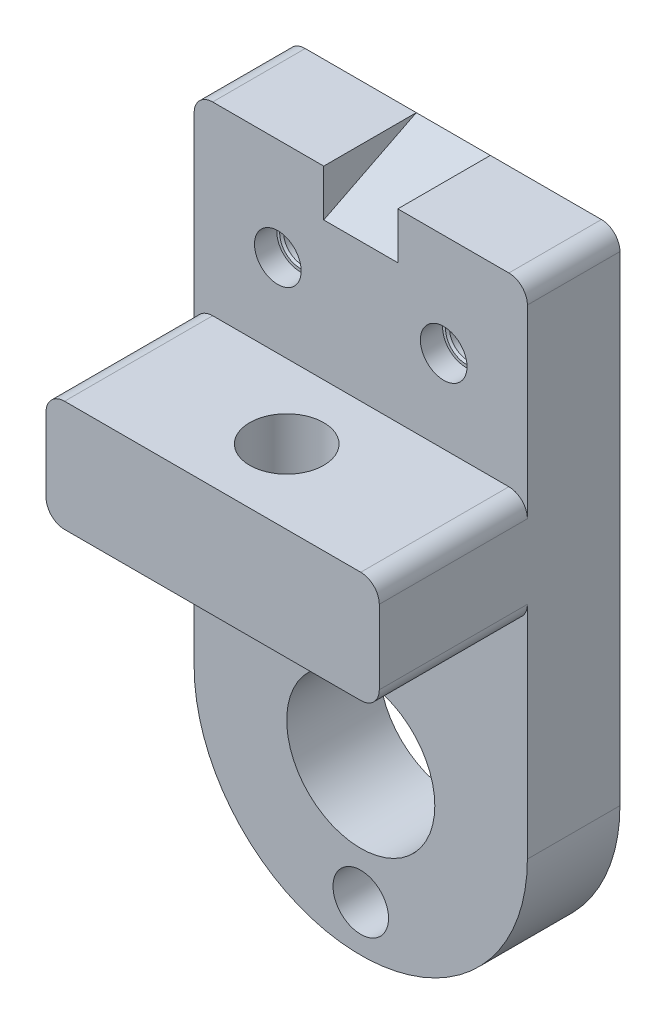
SolidWorks part; units mm, degrees
ref_plane "Alzado" through (0, 0, 0) normal (0, 0, 1) x (1, 0, 0)
ref_plane "Planta" through (0, 0, 0) normal (0, 1, 0) x (1, 0, 0)
ref_plane "Vista lateral" through (0, 0, 0) normal (1, 0, 0) x (0, 0, -1)
sketch "Croquis1" plane through (0, 0, 0) normal (0, 0, 1) x (1, 0, 0)
  line L0 (12.7, 170.942) -> (50.8, 170.942)
  line L1 (-50.8, 170.942) -> (-12.7, 170.942)
  line L2 (-57.15, 164.592) -> (-57.15, 0)
  line L4 (57.15, 164.592) -> (57.15, 0)
  line L5 (-50.8, 69.342) -> (50.8, 69.342)
  line L6 (-57.15, 75.692) -> (-57.15, 101.092)
  line L7 (-50.8, 107.442) -> (50.8, 107.442)
  line L8 (57.15, 75.692) -> (57.15, 101.092)
  line L10 (-12.7, 170.942) -> (-12.7, 154.94)
  line L11 (-12.7, 154.94) -> (12.7, 154.94)
  line L12 (12.7, 170.942) -> (12.7, 154.94)
  arc A0 (-57.15, 0) -> (57.15, 0) centre (0, 0) ccw
  circle A1 centre (0, 0) radius 25.4
  circle A3 centre (0, -41.402) radius 9.525
  arc A6 (-57.15, 101.092) -> (-50.8, 107.442) centre (-50.8, 101.092) cw
  arc A7 (-50.8, 69.342) -> (-57.15, 75.692) centre (-50.8, 75.692) cw
  arc A8 (50.8, 69.342) -> (57.15, 75.692) centre (50.8, 75.692) ccw
  arc A9 (50.8, 107.442) -> (57.15, 101.092) centre (50.8, 101.092) cw
  arc A10 (50.8, 170.942) -> (57.15, 164.592) centre (50.8, 164.592) cw
  arc A11 (-50.8, 170.942) -> (-57.15, 164.592) centre (-50.8, 164.592) ccw
  point P27 (-57.15, 69.342)
  point P32 (57.15, 107.442)
  point P35 (57.15, 170.942)
  dimension "D1" = 57.15
  dimension "D5" = 50.8
  dimension "D6" = 19.05
  dimension "D20" = 6.35
  dimension "D21" = 6.35
  dimension "D22" = 6.35
  dimension "D23" = 6.35
  dimension "D24" = 6.35
  dimension "D25" = 6.35
  dimension "D2" = 170.942
  dimension "D3" = 63.5
  dimension "D4" = 38.1
  dimension "D7" = 41.402
  dimension "D17" = 16.002
  dimension "D18" = 25.4
  dimension "D19" = 44.45
extrude "Saliente-Extruir1" add sketch "Croquis1" along normal blind 31.75 contours L2 L7 L4 L1 | L2 A0 L4 L5 A3 A1 region at (0, 137.6228, 0) region at (55.3975, 37.846, 0)
extrude "Saliente-Extruir2" add sketch "Croquis1<3>" along normal blind 82.55 contours L7 L2 L5 L4 region at (0, 88.392, 0)
sketch "Croquis1<3>" plane through (0, 0, 0) normal (0, 0, 1) x (1, 0, 0) same geometry as "Croquis1"
sketch "Croquis4" plane through (12.7, 0, 0) normal (-1, 0, 0) x (0, 0, 1)
  line L0 (31.75, 154.94) -> (0, 170.942)
  line L1 (0, 170.942) -> (0, 154.94)
  line L2 (0, 154.94) -> (31.75, 154.94)
extrude "Saliente-Extruir3" add sketch "Croquis4" along normal up to next
hole_wizard "Taladro1" positions "Croquis6" profile "Croquis7" legacy end condition through all
sketch "Croquis6" plane through (0, 107.442, 0) normal (0, 1, 0) x (1, 0, 0)
  line L0 (-50.8, -31.75) -> (50.8, -31.75) construction
  line L1 (57.15, -82.55) -> (57.15, -31.75) construction
  point P0 (0, -57.15)
  dimension "D1" = 25.4
  dimension "D2" = 57.15
sketch "Croquis7" plane through (0, 107.442, 57.15) normal (1, 0, 0) x (0, 0, 1)
  line L0 (0, 0) -> (0, 164.592)
  line L1 (0, 164.592) -> (12.7, 164.592)
  line L2 (12.7, 164.592) -> (12.7, 0)
  line L3 (12.7, 0) -> (0, 0)
  line L4 (0, 110) -> (0, -10) construction
  dimension "Diámetro" = 25.4
  dimension "Profundidad" = 164.592
hole_wizard "Refrentado para tornillo con cabeza troncocónica de #01" positions "Croquis8" profile "Croquis10" counterbore size "#0" standard "Ansi Inch" end condition through all
sketch "Croquis8" plane through (0, 0, 31.75) normal (0, 0, 1) x (1, 0, 0)
  line L0 (12.7, 170.942) -> (50.8, 170.942) construction
  line L1 (57.15, 164.592) -> (57.15, 101.092) construction
  line L2 (-57.15, 164.592) -> (-57.15, 101.092) construction
  point P0 (28.448, 135.89)
  point P2 (-28.448, 135.89)
  point P4 (-28.702, 41.402)
  dimension "D1" = 35.052
  dimension "D2" = 28.702
  dimension "D3" = 28.702
  dimension "D4" = 41.402
  dimension "D5" = 28.702
sketch "Croquis10" plane through (28.448, 135.89, 31.75) normal (1, 0, 0) x (0, -1, 0)
  line L0 (0, 0) -> (0, 31.75)
  line L1 (0, 31.75) -> (6.35, 31.75)
  line L2 (6.35, 8.3505) -> (6.35, 31.75)
  line L3 (6.35, 8.3505) -> (6.985, 7.62)
  line L4 (6.985, 7.62) -> (8.001, 7.62)
  line L5 (8.001, 7.62) -> (8.001, 0)
  line L7 (0, 0) -> (8.001, 0)
  line L9 (-6.35, 8.3505) -> (-6.985, 7.62) construction
  line L11 (0, -6.35) -> (0, 107.95) construction
  dimension "Diámetro de taladro hasta el siguiente" = 12.7
  dimension "Profundidad de taladro hasta el siguiente" = 31.75
  dimension "Diámetro de refrentado" = 16.002
  dimension "Profundidad de refrentado" = 7.62
  dimension "Diámetro de avellanado de medio" = 13.97
  dimension "Ángulo de avellanado de medio" = 82
